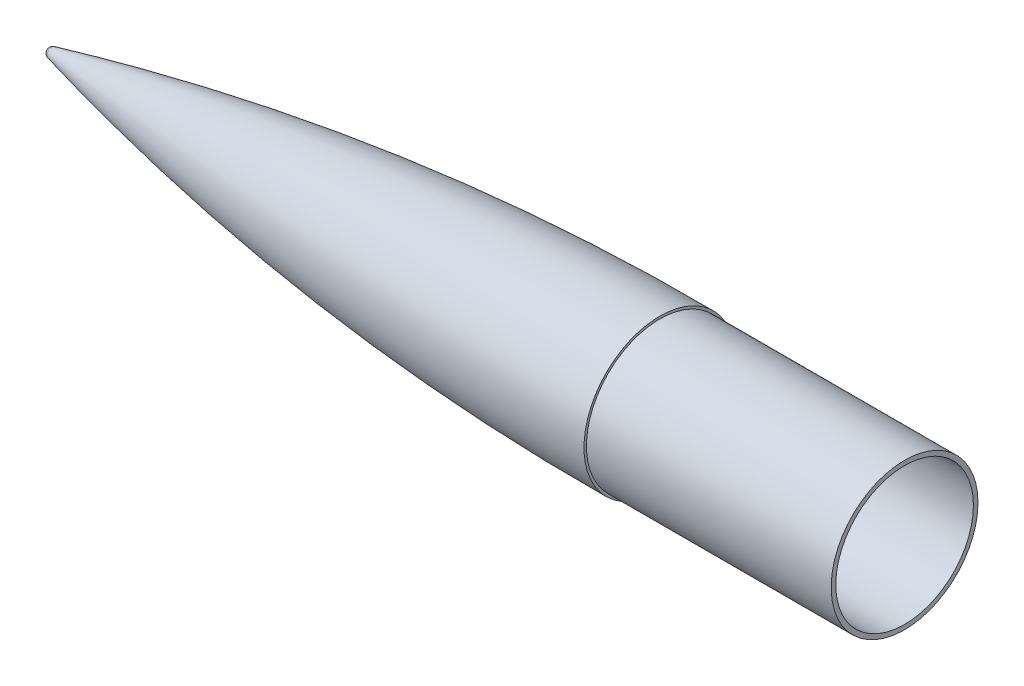
SolidWorks part; units mm, degrees
ref_plane "Front Plane" through (0, 0, 0) normal (0, 0, 1) x (1, 0, 0)
ref_plane "Top Plane" through (0, 0, 0) normal (0, 1, 0) x (1, 0, 0)
ref_plane "Right Plane" through (0, 0, 0) normal (1, 0, 0) x (0, 0, -1)
sketch "Sketch1" plane through (0, 0, 0) normal (0, 0, 1) x (1, 0, 0)
  line L0 (0, 0) -> (13.105, 0) construction
  line L1 (325.525, 0) -> (325.525, 38.1) construction
  line L2 (8.025, 0) -> (8.025, 30.9534) construction
  line L3 (452.525, 0) -> (325.525, 0) construction
  line L4 (325.525, 38.1) -> (452.525, 38.1)
  line L5 (452.525, 38.1) -> (452.525, 35.7187)
  line L6 (325.525, 38.1) -> (325.525, 39.37)
  line L7 (8.025, 0) -> (9.8947, 0)
  line L11 (325.525, 38.1) -> (325.525, 39.37) construction
  line L12 (325.525, 35.7187) -> (452.525, 35.7187)
  line L13 (452.525, 35.7187) -> (452.525, 0) construction
  line L15 (325.525, 35.7187) -> (325.5107, 36.9888)
  line L16 (325.525, 0) -> (13.105, 0) construction
  arc A1 (9.9641, 2.4679) -> (8.025, 0) centre (10.565, 0) ccw
  arc A2 (325.525, 39.37) -> (9.9641, 2.4679) centre (317.6933, -1261.3375) ccw
  arc A3 (13.105, 0) -> (9.9641, 2.4679) centre (10.565, 0) ccw construction
  arc A4 (8.025, 0) -> (13.105, 0) centre (10.565, 0) ccw construction
  arc A5 (8.025, 1.9942) -> (0, 0) centre (317.6933, -1261.3375) ccw construction
  arc A6 (9.9641, 2.4679) -> (8.025, 1.9942) centre (317.6933, -1261.3375) ccw construction
  arc A7 (325.5107, 36.9888) -> (9.8947, 0) centre (317.6933, -1261.3375) ccw
  arc A8 (325.5107, 36.9888) -> (10.5275, 0.1542) centre (317.6933, -1261.3375) ccw construction
  point P4 (10.565, 0)
  point P5 (9.9641, 2.4679)
  point P11 (8.025, 0)
  dimension "D1" = 39.37
  dimension "D2" = 10.565
  dimension "D3" = 2.4679
  dimension "D4" = 9.9641
  dimension "D5" = 317.5
  dimension "D6" = 38.1
  dimension "D7" = 127
  dimension "D8" = 2.3813
  dimension "D9" = 2.3813
revolve "Revolve1" add sketch "Sketch1" angle 360 about L16
equation "\"r_n\"= 0.1'nose tip radius"
equation "\"R_nc\"= 3.1 / 2'nosecone base radius"
equation "\"L_nc\"= 12.5'exposed length of the nosecone"
equation "\"rho\"= ( \"R_nc\" ^ 2 + \"L_nc\" ^ 2 ) / ( 2 * \"R_nc\" )'ogive radius"
equation "\"x_0\"= \"L_nc\" - sqr ( ( \"rho\" - \"r_n\" ) ^ 2 - ( \"rho\" - \"R_nc\" ) ^ 2 )'center of tip sphere"
equation "\"y_t\"= \"r_n\" * ( \"rho\" - \"R_nc\" ) / ( \"rho\" - \"r_n\" )'y-coordinate of tangency point"
equation "\"x_t\"= \"x_0\" - sqr ( \"r_n\" ^ 2 - \"y_t\" ^ 2 )'x-coordinate of tangency point"
equation "\"x_a\"= \"x_0\" - \"r_n\"'apex point"
equation "\"D1@Sketch1\"=\"R_nc\""
equation "\"D2@Sketch1\"=\"x_0\""
equation "\"D3@Sketch1\"=\"y_t\""
equation "\"D4@Sketch1\"=\"x_t\""
equation "\"D5@Sketch1\"=\"L_nc\""
equation "\"t_nc\"= 3 / 32'wall thickness of nosecone"
equation "\"L_s\"= 5'length of shoulder"
equation "\"R_s\"= 3 / 2'radius of shoulder"
equation "\"t_s\"= 3 / 32'wall thickness of shoulder"
equation "\"D6@Sketch1\"=\"R_s\""
equation "\"D8@Sketch1\"=\"t_nc\""
equation "\"D9@Sketch1\"=\"t_s\""
